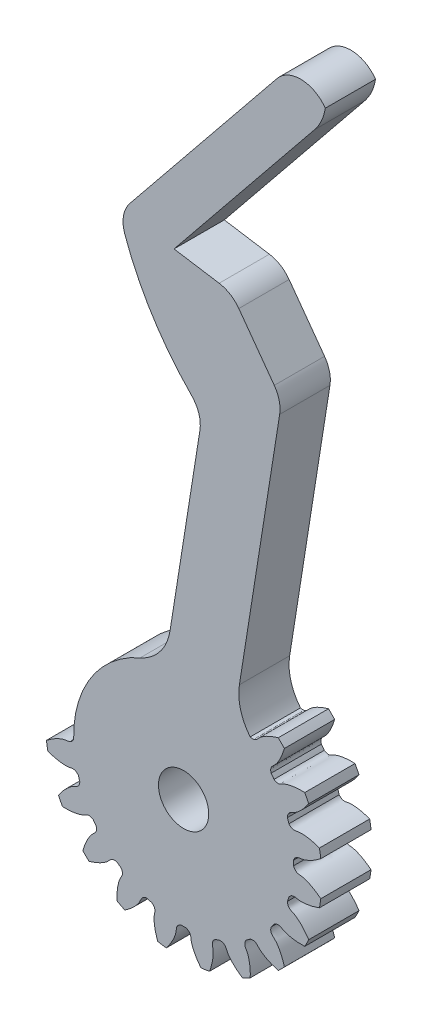
SolidWorks part; units mm, degrees
material "聚脂树脂"
ref_plane "前视基准面" through (0, 0, 0) normal (0, 0, 1) x (1, 0, 0)
ref_plane "上视基准面" through (0, 0, 0) normal (0, 1, 0) x (1, 0, 0)
ref_plane "右视基准面" through (0, 0, 0) normal (1, 0, 0) x (0, 0, -1)
other "Configuration Table"
sketch "草图1" plane through (0, 0, 0) normal (0, 0, 1) x (1, 0, 0)
  circle A0 centre (0, 0) radius 13.75
extrude "凸台-拉伸1" add sketch "草图1" along normal blind 5
ref_axis "基准轴1" through (0, 0, -1.5) along (0, 0, 1)
sketch "草图2" plane through (0, 0, 0) normal (0, 0, 1) x (1, 0, 0)
  line L0 (0, 0) -> (0, 13.75) construction
  circle A0 centre (0, 0) radius 13.75 construction
  arc A1 (0.2416, 10.9348) -> (-0.2416, 10.9348) centre (0, 0) ccw
  arc A2 (3.9764, 15.6228) -> (-3.9764, 15.6228) centre (0, 0) ccw
  spline S0 degree 3 poles (0.2416, 10.9348) (0.764, 11.1168) (0.6964, 11.4839) (0.7661, 11.8375) (0.7736, 11.8719) (0.7829, 11.9108) (0.7941, 11.954) (0.8075, 12.0015) (0.8231, 12.0532) (0.8413, 12.1091) (0.8621, 12.169) (0.8857, 12.2329) (0.9123, 12.3007) (0.9421, 12.3723) (0.9752, 12.4476) (1.0117, 12.5264) (1.0519, 12.6088) (1.0959, 12.6945) (1.1438, 12.7834) (1.1957, 12.8755) (1.2519, 12.9705) (1.3125, 13.0684) (1.3775, 13.1691) (1.4472, 13.2723) (1.5216, 13.3779) (1.601, 13.4858) (1.6853, 13.5958) (1.7747, 13.7078) (1.8694, 13.8216) (1.9693, 13.937) (2.0748, 14.0539) (2.1857, 14.1721) (2.3023, 14.2914) (2.4246, 14.4116) (2.5527, 14.5326) (2.6866, 14.6542) (2.8265, 14.7761) (2.9725, 14.8983) (3.1245, 15.0204) (3.2826, 15.1424) (3.4469, 15.2639) (3.6768, 15.427) (3.8549, 15.5454) (3.9764, 15.6228) knots 0 0 0 0 0.165916 0.170906 0.176664 0.183189 0.190482 0.198542 0.207371 0.216967 0.22733 0.238462 0.250361 0.263027 0.276462 0.290664 0.305634 0.321371 0.337876 0.355149 0.37319 0.391998 0.411574 0.431917 0.453028 0.474907 0.497554 0.520968 0.54515 0.570099 0.595817 0.622302 0.649554 0.677575 0.706363 0.735918 0.766242 0.797333 0.829191 0.861818 0.895212 0.929373 1 1 1 1
  spline S1 degree 3 poles (-0.2416, 10.9348) (-0.764, 11.1168) (-0.6964, 11.4839) (-0.7661, 11.8375) (-0.7736, 11.8719) (-0.7829, 11.9108) (-0.7941, 11.954) (-0.8075, 12.0015) (-0.8231, 12.0532) (-0.8413, 12.1091) (-0.8621, 12.169) (-0.8857, 12.2329) (-0.9123, 12.3007) (-0.9421, 12.3723) (-0.9752, 12.4476) (-1.0117, 12.5264) (-1.0519, 12.6088) (-1.0959, 12.6945) (-1.1438, 12.7834) (-1.1957, 12.8755) (-1.2519, 12.9705) (-1.3125, 13.0684) (-1.3775, 13.1691) (-1.4472, 13.2723) (-1.5216, 13.3779) (-1.601, 13.4858) (-1.6853, 13.5958) (-1.7747, 13.7078) (-1.8694, 13.8216) (-1.9693, 13.937) (-2.0748, 14.0539) (-2.1857, 14.1721) (-2.3023, 14.2914) (-2.4246, 14.4116) (-2.5527, 14.5326) (-2.6866, 14.6542) (-2.8265, 14.7761) (-2.9725, 14.8983) (-3.1245, 15.0204) (-3.2826, 15.1424) (-3.4469, 15.2639) (-3.6768, 15.427) (-3.8549, 15.5454) (-3.9764, 15.6228) knots 0 0 0 0 0.165916 0.170906 0.176664 0.183189 0.190482 0.198542 0.207371 0.216967 0.22733 0.238462 0.250361 0.263027 0.276462 0.290664 0.305634 0.321371 0.337876 0.355149 0.37319 0.391998 0.411574 0.431917 0.453028 0.474907 0.497554 0.520968 0.54515 0.570099 0.595817 0.622302 0.649554 0.677575 0.706363 0.735918 0.766242 0.797333 0.829191 0.861818 0.895212 0.929373 1 1 1 1
extrude "切除-拉伸1" cut sketch "草图2" along normal through all
pattern_circular "阵列(圆周)1" count 20 every 18 about axis through (0, 0, -1.5) along (0, 0, 1) of "切除-拉伸1"
sketch "草图6" plane through (0, 0, 0) normal (0, 0, -1) x (-1, 0, 0)
  line L0 (0, 0) -> (-10.311, 65.1009) construction
  line L1 (0, 0) -> (38.9643, 6.1713) construction
  line L2 (0, 0) -> (-30.4582, -4.8241) construction
  line L3 (-12.3461, -1.9554) -> (-25.9319, 83.8219) construction
  line L4 (3.4569, 0.5475) -> (-2.1703, 36.0761)
  line L5 (-3.4569, -0.5475) -> (-9.0841, 34.981)
  line L6 (-9.0841, 34.981) -> (-15.0031, 72.3522)
  line L7 (-15.0031, 72.3522) -> (-21.4537, 55.5478) construction
  line L8 (-15.0031, 72.3522) -> (-7.9754, 90.6601) construction
  line L9 (-15.0031, 72.3522) -> (-11.6329, 81.132)
  line L10 (-3.4569, -0.5475) -> (3.4569, 0.5475)
  line L11 (-25.2081, 79.2523) -> (-40.1052, 40.4441)
  line L12 (-40.1052, 40.4441) -> (0.9522, 46.947)
  line L13 (0.9522, 46.947) -> (-25.2081, 79.2523)
  line L14 (-15.2883, 74.1529) -> (6.3775, 47.3978)
  line L15 (-15.0031, 72.3522) -> (-15.2883, 74.1529)
  circle A0 centre (0, 0) radius 12.5 construction
  circle A1 centre (-21.4537, 55.5478) radius 24 construction
  circle A2 centre (-21.4537, 55.5478) radius 27.4044 construction
  arc A3 (-11.6329, 81.132) -> (-2.1703, 36.0761) centre (-21.4537, 55.5478) cw
  arc A4 (-12.8529, 77.9537) -> (-9.0841, 34.981) centre (-21.4537, 55.5478) cw
  arc A5 (6.3775, 47.3978) -> (-1.8671, 34.1617) centre (-21.4537, 55.5478) cw
  arc A6 (0.3229, 47.7241) -> (-0.0355, 46.7905) centre (0.9522, 46.947) cw
  dimension "D1" = 25
  dimension "D4" = 48
  dimension "D5" = 30
  dimension "D8" = 29
  dimension "D9" = 1
  dimension "D2" = 7
  dimension "D3" = 58.22
  dimension "D6" = 60
  dimension "D7" = 4.5
extrude "凸台-拉伸2" add sketch "草图6" against normal blind 5 contours A3 L9 L6 L5 L10 L4 | L5 | L4 | A4 L14 L6 L13 | A4 L12 L6 | A6 A4 | A6 L13 A4 | A6 A4 L12 | L15 L9 L14 region at (2.2868, 22.4982, 0) region at (-2.4708, 41.2736, 0) region at (5.8354, 41.9952, 0) region at (-0.4545, 46.5503, 0) region at (-1.3449, 46.7962, 0) region at (6.4238, 59.735, 0) region at (-0.8477, 47.5747, 0) region at (14.9724, 73.28, 0)
ref_plane "基准面1" through (12.5, 0, 0) normal (1, 0, 0) x (0, 0, -1)
ref_axis "基准轴2" through (0, 0, -6) along (0, 0, 1)
ref_plane "基准面2" through (0, 0, 0) normal (-0.9877, 0.1564, 0) x (0, 0, 1)
ref_plane "基准面3" through (12.3461, -1.9554, 0) normal (-0.9877, 0.1564, 0) x (0, 0, 1)
sketch "草图16" plane through (0, 0, 5) normal (0, 0, 1) x (1, 0, 0)
  circle A0 centre (0, 0) radius 2.5
  dimension "D1" = 5
extrude "切除-拉伸5" cut sketch "草图16" against normal blind 16.5
sketch "草图20" plane through (0, 0, 0) normal (0, 0, -1) x (-1, 0, 0)
  line L0 (0, 0) -> (3.6089, 10.325)
  line L1 (3.6089, 10.325) -> (7.1451, 20.4421)
  line L2 (0, 0) -> (10.9348, -0.2416)
  line L3 (10.9348, -0.2416) -> (20.7519, -0.2416)
  circle A0 centre (0, 0) radius 17.5
  circle A1 centre (0, 0) radius 10.9375
  arc A2 (-8.7044, 6.6228) -> (-8.9885, 6.2318) centre (0, 0) ccw construction
  dimension "D1" = 35
extrude "切除-拉伸8" cut sketch "草图20" against normal blind 10 contours A1 L3 A0 L1 region at (-11.1082, 7.7459, 0)
sketch "草图23" plane through (0, 0, 5) normal (0, 0, 1) x (1, 0, 0)
  line L0 (-1.4427, 13.2649) -> (-1.8359, 10.7823)
  line L1 (1.8671, 34.1617) -> (-1.4427, 13.2649) construction
  line L2 (5.4711, 12.1699) -> (5.0779, 9.6873)
  line L3 (10.6873, 45.1034) -> (5.4711, 12.1699) construction
  circle A0 centre (0, 0) radius 10.9375
  arc A1 (-1.7221, 13.6417) -> (-2.5777, 13.5062) centre (0, 0) ccw construction
  arc A2 (-1.7221, 13.6417) -> (-2.5777, 13.5062) centre (0, 0) ccw
  arc A3 (6.6252, 12.0486) -> (5.8534, 12.4419) centre (0, 0) ccw construction
  arc A4 (6.6252, 12.0486) -> (5.8534, 12.4419) centre (0, 0) ccw
  spline S0 degree 3 poles (1994.2556, 137.7507) (-128.5849, -24.5231) (-16.3078, 32.6765) (-1.601, 13.4858) (-1.5216, 13.3779) (9.6576, -2.4852) (-52.1319, -68.6337) (-1962.5686, -374.4069) knots -11.303716 -11.303716 -11.303716 -11.303716 0.502446 0.525093 0.546972 0.568083 10.03707 10.03707 10.03707 10.03707 only from (-1.7221, 13.6417) to (-1.4427, 13.2649) construction
  spline S1 degree 3 poles (-2000.7324, -84.7349) (23.8247, 5.3776) (-2.3586, 6.7359) (-2.931, 11.5081) (-2.9354, 11.558) (-2.9398, 11.6323) (-2.9424, 11.7223) (-2.941, 11.8445) (-2.9339, 11.9853) (-2.9194, 12.1444) (-2.8961, 12.3215) (-2.8626, 12.516) (-2.8175, 12.7274) (-2.7593, 12.9551) (-2.6999, 13.1539) (-2.6447, 13.3205) (5.4121, 36.1167) (129.8707, 16.4119) (-1939.2458, -485.2572) knots -2.172632 -2.172632 -2.172632 -2.172632 0.165916 0.170906 0.183189 0.190482 0.207371 0.22733 0.250361 0.276462 0.305634 0.337876 0.37319 0.411574 0.453028 0.474907 0.497554 12.30377 12.30377 12.30377 12.30377 only from (-3.1492, 10.4743) to (-2.5777, 13.5062) construction
  spline S2 degree 3 poles (-1.7221, 13.6417) (-1.653, 13.5549) (-1.5584, 13.4302) (-1.4684, 13.3023) (-1.4427, 13.2649) knots 0.492568 0.492568 0.492568 0.492568 0.546972 0.569233 0.569233 0.569233 0.569233
  spline S3 degree 3 poles (-3.1492, 10.4743) (-2.7087, 10.8088) (-2.8864, 11.137) (-2.931, 11.5081) (-2.9354, 11.558) (-2.9398, 11.6323) (-2.9424, 11.7223) (-2.941, 11.8445) (-2.9339, 11.9853) (-2.9194, 12.1444) (-2.8961, 12.3215) (-2.8626, 12.516) (-2.8175, 12.7274) (-2.7593, 12.9551) (-2.6866, 13.1982) (-2.6232, 13.3832) (-2.5848, 13.4873) (-2.5777, 13.5062) knots 0 0 0 0 0.165916 0.170906 0.183189 0.190482 0.207371 0.22733 0.250361 0.276462 0.305634 0.337876 0.37319 0.411574 0.453028 0.497554 0.507432 0.507432 0.507432 0.507432
  spline S4 degree 3 poles (1694.4124, -1060.787) (-118.4443, 55.7411) (6.0134, 36.0216) (6.6326, 11.8082) (6.6318, 11.5928) (6.6211, 11.3487) (6.6022, 11.1239) (6.5767, 10.9187) (6.5461, 10.7332) (6.5119, 10.5675) (6.4757, 10.4216) (6.4439, 10.3125) (6.4137, 10.2194) (6.3905, 10.1545) (6.3633, 10.0853) (6.3437, 10.0391) (4.3246, 5.6774) (-20.9966, 12.4766) (1876.592, -698.8356) knots -11.303841 -11.303841 -11.303841 -11.303841 0.502446 0.525093 0.568083 0.608002 0.644851 0.678629 0.709336 0.736973 0.761538 0.783033 0.792629 0.809518 0.816811 0.829094 0.834084 3.172618 3.172618 3.172618 3.172618 only from (6.6252, 12.0486) to (6.2318, 8.9885) construction
  spline S5 degree 3 poles (1750.7751, -962.5282) (28.3709, -81.3829) (-9.9528, 0.6209) (5.5812, 12.2529) (5.6899, 12.331) (25.6072, 26.0377) (114.7128, -63.0571) (-1854.0616, 747.259) knots -9.036996 -9.036996 -9.036996 -9.036996 0.431917 0.453028 0.474907 0.497554 12.303674 12.303674 12.303674 12.303674 only from (5.4711, 12.1699) to (5.8534, 12.4419) construction
  spline S6 degree 3 poles (6.6252, 12.0486) (6.6301, 11.9377) (6.6341, 11.7422) (6.6276, 11.4683) (6.6126, 11.2338) (6.5902, 11.0188) (6.5619, 10.8235) (6.5293, 10.6479) (6.4939, 10.4921) (6.4623, 10.3749) (6.4317, 10.2737) (6.4078, 10.2024) (6.3839, 10.1378) (6.3633, 10.0853) (6.3437, 10.0391) (6.1867, 9.7) (5.9162, 9.4428) (6.2318, 8.9885) knots 0.492568 0.492568 0.492568 0.492568 0.546972 0.588426 0.62681 0.662124 0.694366 0.723538 0.749639 0.77267 0.783033 0.801458 0.809518 0.816811 0.829094 0.834084 1 1 1 1
  spline S7 degree 3 poles (5.4711, 12.1699) (5.5426, 12.2247) (5.6688, 12.3172) (5.798, 12.4053) (5.8534, 12.4419) knots 0.430767 0.430767 0.430767 0.430767 0.474907 0.507432 0.507432 0.507432 0.507432
extrude "切除-拉伸10" cut sketch "草图23" against normal blind 10 contours S3 A0 L0 S2 A2 | S7 L2 A0 S6 A4 region at (-2.2448, 12.1367, 5) region at (5.8854, 10.849, 5)
fillet "圆角7" radius 5 2 edges at (5.0779, 9.6873, 2.5) (-1.8359, 10.7823, 2.5)
fillet "圆角8" radius 3 2 edges at (1.8671, 34.1617, 2.5) (-6.3775, 47.3978, 2.5)
chamfer "倒角1" distance 6 angle 45 1 edges at (10.6873, 45.1034, 2.5)
fillet "圆角10" radius 3 2 edges at (9.7487, 39.1773, 2.5) (4.7612, 46.042, 2.5)
fillet "圆角11" radius 5 1 edges at (13.8804, 65.2637, 2.5)
fillet "圆角12" radius 3 1 edges at (15.2883, 74.1529, 2.5)
